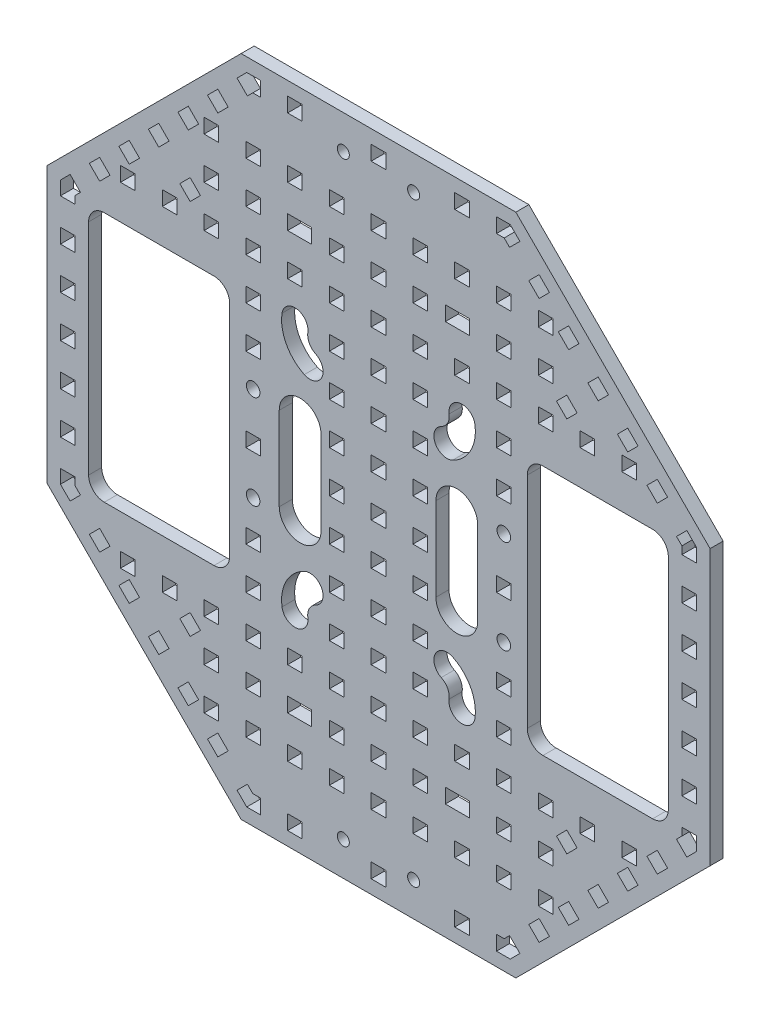
SolidWorks part; units mm, degrees
ref_plane "Plano frontal" through (0, 0, 0) normal (0, 0, 1) x (1, 0, 0)
ref_plane "Plano superior" through (0, 0, 0) normal (0, 1, 0) x (1, 0, 0)
ref_plane "Plano direito" through (0, 0, 0) normal (1, 0, 0) x (0, 0, -1)
sketch "Esboço1" plane through (0, 0, 0) normal (0, 0, 1) x (1, 0, 0)
  line L1 (63.5, -26.3026) -> (63.5, 26.3026)
  line L2 (63.5, 26.3026) -> (26.3026, 63.5)
  line L3 (26.3026, 63.5) -> (-26.3026, 63.5)
  line L4 (-26.3026, 63.5) -> (-63.5, 26.3026)
  line L5 (-63.5, 26.3026) -> (-63.5, -26.3026)
  line L6 (-63.5, -26.3026) -> (-26.3026, -63.5)
  line L7 (-26.3026, -63.5) -> (26.3026, -63.5)
  line L8 (26.3026, -63.5) -> (63.5, -26.3026)
  circle A0 centre (0, 0) radius 63.5 construction
  dimension "D1" = 127
extrude "Ressalto-extrusão1" add sketch "Esboço1" along normal blind 2.5
sketch "Esboço3"
sketch "Esboço2" plane through (0, 0, 0) normal (0, 0, -1) x (-1, 0, 0)
  line L0 (-42, 0) -> (42, 0) construction
  line L1 (-24, 0) -> (24, 0) construction
  line L2 (24, 0) -> (24, 9) construction
  line L3 (0, 0) -> (0, 75.734) construction
  line L4 (52.5, 24) -> (31.5, 24)
  line L5 (55.5, 21) -> (55.5, -21)
  line L6 (52.5, -24) -> (31.5, -24)
  line L7 (28.5, 21) -> (28.5, -21)
  line L8 (55.5, 24) -> (28.5, -24) construction
  line L9 (55.5, -24) -> (28.5, 24) construction
  line L10 (-55.5, -24) -> (-28.5, 24) construction
  line L11 (-55.5, 24) -> (-28.5, -24) construction
  line L12 (-24, 0) -> (-24, 9) construction
  line L13 (-28.5, 21) -> (-28.5, -21)
  line L14 (-52.5, -24) -> (-31.5, -24)
  line L15 (-55.5, 21) -> (-55.5, -21)
  line L16 (-52.5, 24) -> (-31.5, 24)
  line L17 (0, 0) -> (0, -57) construction
  line L18 (0, -57) -> (-6.731, -57) construction
  line L19 (0, 63.5) -> (0, 43.5) construction
  line L20 (-26.3026, 63.5) -> (26.3026, 63.5) construction
  line L29 (63.5, 0) -> (-63.5, 0) construction
  line L30 (63.5, 26.3026) -> (63.5, -26.3026) construction
  line L31 (-63.5, -26.3026) -> (-63.5, 26.3026) construction
  circle A0 centre (24, 9) radius 1.3
  circle A1 centre (24, -9) radius 1.3
  arc A2 (31.5, 24) -> (28.5, 21) centre (31.5, 21) ccw
  arc A3 (31.5, -24) -> (28.5, -21) centre (31.5, -21) cw
  arc A4 (55.5, -21) -> (52.5, -24) centre (52.5, -21) cw
  arc A5 (52.5, 24) -> (55.5, 21) centre (52.5, 21) cw
  arc A6 (-52.5, 24) -> (-55.5, 21) centre (-52.5, 21) ccw
  arc A7 (-55.5, -21) -> (-52.5, -24) centre (-52.5, -21) ccw
  arc A8 (-31.5, -24) -> (-28.5, -21) centre (-31.5, -21) ccw
  arc A9 (-31.5, 24) -> (-28.5, 21) centre (-31.5, 21) cw
  circle A10 centre (-24, -9) radius 1.3
  circle A11 centre (-24, 9) radius 1.3
  circle A12 centre (-6.731, -57) radius 1.15
  circle A13 centre (6.731, -57) radius 1.15
  circle A14 centre (6.731, 57) radius 1.15
  circle A15 centre (-6.731, 57) radius 1.15
  dimension "D6" = 3
  dimension "D8" = 6.731
  dimension "D12" = 9
  dimension "D1" = 42
  dimension "D2" = 48
  dimension "D3" = 27
  dimension "D4" = 24
  dimension "D5" = 9
  dimension "D7" = 57
extrude "Corte-extrusão1" cut sketch "Esboço2" against normal through all
sketch "Esboço4" plane through (0, 0, 2.5) normal (0, 0, 1) x (1, 0, 0)
  line L0 (0, 0) -> (36.0624, 36.0624) construction
  line L1 (0, 0) -> (36.0624, -36.0624) construction
  line L2 (0, 0) -> (-36.0624, -36.0624) construction
  line L3 (0, 0) -> (-36.0624, 36.0624) construction
  line L4 (-38.0423, 36.0624) -> (-34.0825, 36.0624) construction
  line L11 (-36.0624, 34.0825) -> (-36.0624, 38.0423) construction
  line L12 (-36.0624, 34.0825) -> (-34.0825, 36.0624)
  line L13 (-38.0423, 36.0624) -> (-36.0624, 34.0825)
  line L14 (-36.0624, 38.0423) -> (-34.0825, 36.0624)
  line L15 (-38.0423, 36.0624) -> (-36.0624, 38.0423)
  line L16 (34.0825, 36.0624) -> (38.0423, 36.0624) construction
  line L17 (36.0624, 34.0825) -> (36.0624, 38.0423) construction
  line L18 (36.0624, 34.0825) -> (38.0423, 36.0624)
  line L19 (34.0825, 36.0624) -> (36.0624, 34.0825)
  line L20 (36.0624, 38.0423) -> (38.0423, 36.0624)
  line L21 (34.0825, 36.0624) -> (36.0624, 38.0423)
  line L22 (34.0825, -36.0624) -> (38.0423, -36.0624) construction
  line L23 (36.0624, -38.0423) -> (36.0624, -34.0825) construction
  line L24 (36.0624, -38.0423) -> (38.0423, -36.0624)
  line L25 (34.0825, -36.0624) -> (36.0624, -38.0423)
  line L26 (36.0624, -34.0825) -> (38.0423, -36.0624)
  line L27 (34.0825, -36.0624) -> (36.0624, -34.0825)
  line L28 (-38.0423, -36.0624) -> (-34.0825, -36.0624) construction
  line L29 (-36.0624, -38.0423) -> (-36.0624, -34.0825) construction
  line L30 (-36.0624, -38.0423) -> (-34.0825, -36.0624)
  line L31 (-38.0423, -36.0624) -> (-36.0624, -38.0423)
  line L32 (-36.0624, -34.0825) -> (-34.0825, -36.0624)
  line L33 (-38.0423, -36.0624) -> (-36.0624, -34.0825)
  circle A0 centre (0, 0) radius 51 construction
  circle A1 centre (-36.0624, 36.0624) radius 1.65 construction
  circle A2 centre (36.0624, 36.0624) radius 1.65 construction
  circle A3 centre (36.0624, -36.0624) radius 1.65 construction
  circle A4 centre (-36.0624, -36.0624) radius 1.65 construction
  point P10 (0, 0)
  point P17 (0, 0)
  point P21 (-36.0624, 36.0624)
  point P26 (36.0624, 36.0624)
  point P31 (36.0624, -36.0624)
  point P36 (-36.0624, -36.0624)
  dimension "D1" = 4
  dimension "D2" = 4
  dimension "D4" = 2.8
  dimension "D5" = 2.8
  dimension "D6" = 2.8
  dimension "D7" = 2.8
extrude "Corte-extrusão2" cut sketch "Esboço4" against normal blind 10.5
sketch "Esboço5" plane through (0, 0, 0) normal (0, 0, -1) x (-1, 0, 0)
  line L0 (-44.9013, -44.9013) -> (-42.0729, -42.0729) construction
  line L1 (-26.3026, -63.5) -> (-63.5, -26.3026) construction
  line L2 (-47.7297, -34.4361) -> (-49.7096, -36.416)
  line L3 (-42.0729, -40.093) -> (-44.0528, -42.0729)
  line L4 (-42.0729, -40.093) -> (-40.093, -42.0729)
  line L5 (-40.093, -42.0729) -> (-42.0729, -44.0528)
  line L6 (-44.0528, -42.0729) -> (-42.0729, -44.0528)
  line L7 (-42.0729, -40.093) -> (-42.0729, -44.0528) construction
  line L8 (-40.093, -42.0729) -> (-44.0528, -42.0729) construction
  line L9 (-47.7297, -34.4361) -> (-45.7498, -36.416)
  line L10 (-45.7498, -36.416) -> (-47.7297, -38.3959)
  line L11 (-49.7096, -36.416) -> (-47.7297, -38.3959)
  line L12 (-47.7297, -34.4361) -> (-47.7297, -38.3959) construction
  line L13 (-45.7498, -36.416) -> (-49.7096, -36.416) construction
  line L14 (-53.3866, -28.7792) -> (-55.3665, -30.7591)
  line L15 (-53.3866, -28.7792) -> (-51.4067, -30.7591)
  line L16 (-51.4067, -30.7591) -> (-53.3866, -32.739)
  line L17 (-55.3665, -30.7591) -> (-53.3866, -32.739)
  line L18 (-53.3866, -28.7792) -> (-53.3866, -32.739) construction
  line L19 (-51.4067, -30.7591) -> (-55.3665, -30.7591) construction
  line L20 (-63.5, -26.3026) -> (-63.5, 26.3026) construction
  line L21 (63.5, 26.3026) -> (63.5, -26.3026) construction
  line L22 (-16, 24) -> (0, 24) construction
  line L23 (0, 24) -> (16, 24) construction
  line L24 (-9.4, 22.6) -> (-6.6, 25.4) construction
  line L25 (-9.4, 25.4) -> (-9.4, 22.6)
  line L26 (-9.4, 22.6) -> (-6.6, 22.6)
  line L27 (-9.4, 25.4) -> (-6.6, 22.6) construction
  line L28 (-30.7591, -51.4067) -> (-30.7591, -55.3665) construction
  line L29 (-28.7792, -53.3866) -> (-32.739, -53.3866) construction
  line L30 (-36.416, -45.7498) -> (-36.416, -49.7096) construction
  line L31 (-34.4361, -47.7297) -> (-38.3959, -47.7297) construction
  line L32 (-42.0729, -40.093) -> (-42.0729, -44.0528) construction
  line L33 (-40.093, -42.0729) -> (-44.0528, -42.0729) construction
  line L34 (-25.2256, -60.9) -> (-27.0822, -59.0434)
  line L35 (-25.1023, -57.0635) -> (-27.0822, -59.0434)
  line L36 (-9.4, 25.4) -> (-6.6, 25.4)
  line L37 (-6.6, 25.4) -> (-6.6, 22.6)
  line L38 (-30.7591, -55.3665) -> (-32.739, -53.3866)
  line L39 (-30.7591, -51.4067) -> (-32.739, -53.3866)
  line L40 (-28.7792, -53.3866) -> (-30.7591, -51.4067)
  line L41 (-28.7792, -53.3866) -> (-30.7591, -55.3665)
  line L42 (-36.416, -49.7096) -> (-38.3959, -47.7297)
  line L43 (-36.416, -45.7498) -> (-38.3959, -47.7297)
  line L44 (-34.4361, -47.7297) -> (-36.416, -45.7498)
  line L45 (-58.1, 6.6) -> (-60.9, 9.4) construction
  line L46 (-60.9, 6.6) -> (-58.1, 9.4) construction
  line L47 (-34.4361, -47.7297) -> (-36.416, -49.7096)
  line L48 (0, -63.5) -> (0, -59.5) construction
  line L49 (26.3026, -63.5) -> (-26.3026, -63.5) construction
  line L50 (-9.4, 6.6) -> (-6.6, 6.6)
  line L51 (1.4, -58.1) -> (-1.4, -58.1)
  line L52 (1.4, -58.1) -> (1.4, -60.9)
  line L53 (1.4, -60.9) -> (-1.4, -60.9)
  line L54 (-1.4, -58.1) -> (-1.4, -60.9)
  line L55 (1.4, -58.1) -> (-1.4, -60.9) construction
  line L56 (1.4, -60.9) -> (-1.4, -58.1) construction
  line L57 (-6.6, 9.4) -> (-6.6, 6.6)
  line L58 (-9.4, 9.4) -> (-6.6, 9.4)
  line L59 (-9.4, 9.4) -> (-9.4, 6.6)
  line L60 (-9.4, 6.6) -> (-6.6, 9.4) construction
  line L61 (-9.4, 9.4) -> (-6.6, 6.6) construction
  line L62 (-14.6, -58.1) -> (-17.4, -58.1)
  line L63 (-14.6, -58.1) -> (-14.6, -60.9)
  line L64 (-14.6, -60.9) -> (-17.4, -60.9)
  line L65 (-17.4, -58.1) -> (-17.4, -60.9)
  line L66 (-14.6, -58.1) -> (-17.4, -60.9) construction
  line L67 (-14.6, -60.9) -> (-17.4, -58.1) construction
  line L68 (-22.6, -58.1) -> (-24.0658, -58.1)
  line L69 (-22.6, -58.1) -> (-22.6, -60.9)
  line L70 (-22.6, -60.9) -> (-25.2256, -60.9)
  line L71 (6.6, 22.6) -> (9.4, 25.4) construction
  line L72 (6.6, 25.4) -> (6.6, 22.6)
  line L73 (6.6, 22.6) -> (9.4, 22.6)
  line L74 (6.6, 25.4) -> (9.4, 22.6) construction
  line L75 (6.6, 25.4) -> (9.4, 25.4)
  line L76 (9.4, 25.4) -> (9.4, 22.6)
  line L77 (-9.4, -1.4) -> (-6.6, -1.4)
  line L78 (-25.4, -58.1) -> (-25.4, -59.0434) [skipped]
  line L79 (-33.4, 46.6) -> (-30.6, 49.4) construction
  line L80 (-24.0658, -58.1) -> (-25.1023, -57.0635)
  line L81 (-33.4, 49.4) -> (-30.6, 46.6) construction
  line L82 (-23.5434, -59.0434) -> (-24, -59.5) construction
  line L83 (-25.4, 46.6) -> (-22.6, 49.4) construction
  line L84 (-24, -59.5) -> (-24.4566, -59.0434) construction
  line L85 (6.6, -25.4) -> (9.4, -22.6) construction
  line L86 (6.6, -22.6) -> (9.4, -25.4) construction
  line L87 (9.4, -25.4) -> (9.4, -22.6)
  line L88 (6.6, -25.4) -> (9.4, -25.4)
  line L89 (6.6, -22.6) -> (9.4, -22.6)
  line L90 (6.6, -25.4) -> (6.6, -22.6)
  line L91 (-9.4, -25.4) -> (-6.6, -22.6) construction
  line L92 (-9.4, -22.6) -> (-6.6, -25.4) construction
  line L93 (-6.6, -25.4) -> (-6.6, -22.6)
  line L94 (-9.4, -25.4) -> (-6.6, -25.4)
  line L95 (-9.4, -22.6) -> (-6.6, -22.6)
  line L96 (-9.4, -25.4) -> (-9.4, -22.6)
  line L97 (-60.25, 0) -> (60.25, 0) construction
  line L98 (0, 0) -> (0, 63.5) construction
  line L99 (-26.3026, 63.5) -> (26.3026, 63.5) construction
  line L100 (-25.4, 49.4) -> (-22.6, 46.6) construction
  line L101 (-6.6, 1.4) -> (-6.6, -1.4)
  line L102 (-9.4, 1.4) -> (-6.6, 1.4)
  line L103 (-9.4, 1.4) -> (-9.4, -1.4)
  line L104 (-9.4, -1.4) -> (-6.6, 1.4) construction
  line L105 (-9.4, 1.4) -> (-6.6, -1.4) construction
  line L106 (14.6, -60.9) -> (17.4, -58.1) construction
  line L107 (14.6, -58.1) -> (17.4, -60.9) construction
  line L108 (-9.4, -9.4) -> (-6.6, -9.4)
  line L109 (-6.6, -6.6) -> (-6.6, -9.4)
  line L110 (40.093, -42.0729) -> (44.0528, -42.0729) construction
  line L111 (42.0729, -40.093) -> (42.0729, -44.0528) construction
  line L112 (34.4361, -47.7297) -> (38.3959, -47.7297) construction
  line L113 (36.416, -45.7498) -> (36.416, -49.7096) construction
  line L114 (28.7792, -53.3866) -> (32.739, -53.3866) construction
  line L115 (30.7591, -51.4067) -> (30.7591, -55.3665) construction
  line L116 (-9.4, -6.6) -> (-6.6, -6.6)
  line L117 (-9.4, -6.6) -> (-9.4, -9.4)
  line L118 (-9.4, -9.4) -> (-6.6, -6.6) construction
  line L119 (51.4067, -30.7591) -> (55.3665, -30.7591) construction
  line L120 (53.3866, -28.7792) -> (53.3866, -32.739) construction
  line L121 (45.7498, -36.416) -> (49.7096, -36.416) construction
  line L122 (47.7297, -34.4361) -> (47.7297, -38.3959) construction
  line L123 (40.093, -42.0729) -> (44.0528, -42.0729) construction
  line L124 (42.0729, -40.093) -> (42.0729, -44.0528) construction
  line L125 (44.9013, -44.9013) -> (42.0729, -42.0729) construction
  line L126 (-9.4, -6.6) -> (-6.6, -9.4) construction
  line L127 (9.4, -6.6) -> (6.6, -9.4) construction
  line L128 (9.4, -9.4) -> (6.6, -6.6) construction
  line L129 (9.4, 1.4) -> (6.6, -1.4) construction
  line L130 (9.4, -1.4) -> (6.6, 1.4) construction
  line L131 (9.4, 9.4) -> (6.6, 6.6) construction
  line L132 (9.4, 6.6) -> (6.6, 9.4) construction
  line L133 (24.0658, -58.1) -> (25.1023, -57.0635)
  line L134 (60.9, -25.2256) -> (59.0434, -27.0822)
  line L135 (57.0635, -25.1023) -> (59.0434, -27.0822)
  line L136 (58.1, -6.6) -> (58.1, -9.4)
  line L137 (58.1, 1.4) -> (58.1, -1.4)
  line L138 (22.6, -60.9) -> (25.2256, -60.9)
  line L139 (22.6, -58.1) -> (22.6, -60.9)
  line L140 (22.6, -58.1) -> (24.0658, -58.1)
  line L141 (17.4, -58.1) -> (17.4, -60.9)
  line L142 (14.6, -60.9) -> (17.4, -60.9)
  line L143 (14.6, -58.1) -> (14.6, -60.9)
  line L144 (14.6, -58.1) -> (17.4, -58.1)
  line L145 (9.4, -6.6) -> (9.4, -9.4)
  line L146 (9.4, -6.6) -> (6.6, -6.6)
  line L147 (6.6, -6.6) -> (6.6, -9.4)
  line L148 (9.4, -9.4) -> (6.6, -9.4)
  line L149 (34.4361, -47.7297) -> (36.416, -49.7096)
  line L150 (40.093, -42.0729) -> (42.0729, -44.0528)
  line L151 (42.0729, -40.093) -> (44.0528, -42.0729)
  line L152 (34.4361, -47.7297) -> (36.416, -45.7498)
  line L153 (36.416, -45.7498) -> (38.3959, -47.7297)
  line L154 (36.416, -49.7096) -> (38.3959, -47.7297)
  line L155 (28.7792, -53.3866) -> (30.7591, -55.3665)
  line L156 (28.7792, -53.3866) -> (30.7591, -51.4067)
  line L157 (30.7591, -51.4067) -> (32.739, -53.3866)
  line L158 (30.7591, -55.3665) -> (32.739, -53.3866)
  line L159 (58.1, 1.4) -> (60.9, 1.4)
  line L160 (25.1023, -57.0635) -> (27.0822, -59.0434)
  line L161 (25.2256, -60.9) -> (27.0822, -59.0434)
  line L162 (60.9, 1.4) -> (60.9, -1.4)
  line L163 (58.1, -1.4) -> (60.9, -1.4)
  line L164 (58.1, -6.6) -> (60.9, -6.6)
  line L165 (60.9, -6.6) -> (60.9, -9.4)
  line L166 (55.3665, -30.7591) -> (53.3866, -32.739)
  line L167 (51.4067, -30.7591) -> (53.3866, -32.739)
  line L168 (53.3866, -28.7792) -> (51.4067, -30.7591)
  line L169 (53.3866, -28.7792) -> (55.3665, -30.7591)
  line L170 (49.7096, -36.416) -> (47.7297, -38.3959)
  line L171 (45.7498, -36.416) -> (47.7297, -38.3959)
  line L172 (47.7297, -34.4361) -> (45.7498, -36.416)
  line L173 (44.0528, -42.0729) -> (42.0729, -44.0528)
  line L174 (-58.1, 14.6) -> (-60.9, 17.4) construction
  line L175 (42.0729, -40.093) -> (40.093, -42.0729)
  line L176 (-60.9, 14.6) -> (-58.1, 17.4) construction
  line L177 (47.7297, -34.4361) -> (49.7096, -36.416)
  line L178 (44.9013, 44.9013) -> (42.0729, 42.0729) construction
  line L179 (42.0729, 40.093) -> (42.0729, 44.0528) construction
  line L180 (40.093, 42.0729) -> (44.0528, 42.0729) construction
  line L181 (47.7297, 34.4361) -> (47.7297, 38.3959) construction
  line L182 (45.7498, 36.416) -> (49.7096, 36.416) construction
  line L183 (53.3866, 28.7792) -> (53.3866, 32.739) construction
  line L184 (51.4067, 30.7591) -> (55.3665, 30.7591) construction
  line L185 (58.1, -9.4) -> (60.9, -9.4)
  line L186 (58.1, -14.6) -> (58.1, -17.4)
  line L187 (30.7591, 51.4067) -> (30.7591, 55.3665) construction
  line L188 (28.7792, 53.3866) -> (32.739, 53.3866) construction
  line L189 (36.416, 45.7498) -> (36.416, 49.7096) construction
  line L190 (34.4361, 47.7297) -> (38.3959, 47.7297) construction
  line L191 (42.0729, 40.093) -> (42.0729, 44.0528) construction
  line L192 (40.093, 42.0729) -> (44.0528, 42.0729) construction
  line L193 (9.4, 1.4) -> (9.4, -1.4)
  line L194 (9.4, 1.4) -> (6.6, 1.4)
  line L195 (14.6, 58.1) -> (17.4, 60.9) construction
  line L196 (14.6, 60.9) -> (17.4, 58.1) construction
  line L197 (58.1, -14.6) -> (60.9, -14.6)
  line L198 (60.9, -14.6) -> (60.9, -17.4)
  line L199 (58.1, -17.4) -> (60.9, -17.4)
  line L200 (58.1, -22.6) -> (58.1, -24.0658)
  line L201 (58.1, -22.6) -> (60.9, -22.6)
  line L202 (60.9, -22.6) -> (60.9, -25.2256)
  line L203 (58.1, -24.0658) -> (57.0635, -25.1023)
  line L204 (58.1, 24.0658) -> (57.0635, 25.1023)
  line L205 (-14.6, 60.9) -> (-17.4, 58.1) construction
  line L206 (-14.6, 58.1) -> (-17.4, 60.9) construction
  line L207 (6.6, 1.4) -> (6.6, -1.4)
  line L208 (9.4, -1.4) -> (6.6, -1.4)
  line L209 (1.4, 60.9) -> (-1.4, 58.1) construction
  line L210 (1.4, 58.1) -> (-1.4, 60.9) construction
  line L211 (0, 63.5) -> (0, 59.5) construction
  line L212 (-40.093, 42.0729) -> (-44.0528, 42.0729) construction
  line L213 (-42.0729, 40.093) -> (-42.0729, 44.0528) construction
  line L214 (-34.4361, 47.7297) -> (-38.3959, 47.7297) construction
  line L215 (-36.416, 45.7498) -> (-36.416, 49.7096) construction
  line L216 (-28.7792, 53.3866) -> (-32.739, 53.3866) construction
  line L217 (-30.7591, 51.4067) -> (-30.7591, 55.3665) construction
  line L218 (60.9, 22.6) -> (60.9, 25.2256)
  line L219 (58.1, 22.6) -> (60.9, 22.6)
  line L220 (-51.4067, 30.7591) -> (-55.3665, 30.7591) construction
  line L221 (-53.3866, 28.7792) -> (-53.3866, 32.739) construction
  line L222 (-45.7498, 36.416) -> (-49.7096, 36.416) construction
  line L223 (-47.7297, 34.4361) -> (-47.7297, 38.3959) construction
  line L224 (-40.093, 42.0729) -> (-44.0528, 42.0729) construction
  line L225 (-42.0729, 40.093) -> (-42.0729, 44.0528) construction
  line L226 (-44.9013, 44.9013) -> (-42.0729, 42.0729) construction
  line L227 (47.7297, 34.4361) -> (49.7096, 36.416)
  line L228 (42.0729, 40.093) -> (44.0528, 42.0729)
  line L229 (42.0729, 40.093) -> (40.093, 42.0729)
  line L230 (40.093, 42.0729) -> (42.0729, 44.0528)
  line L231 (44.0528, 42.0729) -> (42.0729, 44.0528)
  line L232 (47.7297, 34.4361) -> (45.7498, 36.416)
  line L233 (45.7498, 36.416) -> (47.7297, 38.3959)
  line L234 (49.7096, 36.416) -> (47.7297, 38.3959)
  line L235 (53.3866, 28.7792) -> (55.3665, 30.7591)
  line L236 (53.3866, 28.7792) -> (51.4067, 30.7591)
  line L237 (51.4067, 30.7591) -> (53.3866, 32.739)
  line L238 (55.3665, 30.7591) -> (53.3866, 32.739)
  line L239 (58.1, 22.6) -> (58.1, 24.0658)
  line L240 (58.1, 17.4) -> (60.9, 17.4)
  line L241 (60.9, 14.6) -> (60.9, 17.4)
  line L242 (58.1, 14.6) -> (60.9, 14.6)
  line L243 (25.2256, 60.9) -> (27.0822, 59.0434)
  line L244 (25.1023, 57.0635) -> (27.0822, 59.0434)
  line L245 (58.1, 14.6) -> (58.1, 17.4)
  line L246 (30.7591, 55.3665) -> (32.739, 53.3866)
  line L247 (30.7591, 51.4067) -> (32.739, 53.3866)
  line L248 (28.7792, 53.3866) -> (30.7591, 51.4067)
  line L249 (28.7792, 53.3866) -> (30.7591, 55.3665)
  line L250 (36.416, 49.7096) -> (38.3959, 47.7297)
  line L251 (36.416, 45.7498) -> (38.3959, 47.7297)
  line L252 (34.4361, 47.7297) -> (36.416, 45.7498)
  line L253 (-60.9, -14.6) -> (-58.1, -17.4) construction
  line L254 (-58.1, -14.6) -> (-60.9, -17.4) construction
  line L255 (34.4361, 47.7297) -> (36.416, 49.7096)
  line L256 (9.4, 9.4) -> (9.4, 6.6)
  line L257 (9.4, 9.4) -> (6.6, 9.4)
  line L258 (6.6, 9.4) -> (6.6, 6.6)
  line L259 (9.4, 6.6) -> (6.6, 6.6)
  line L260 (14.6, 58.1) -> (17.4, 58.1)
  line L261 (14.6, 58.1) -> (14.6, 60.9)
  line L262 (14.6, 60.9) -> (17.4, 60.9)
  line L263 (17.4, 58.1) -> (17.4, 60.9)
  line L264 (22.6, 58.1) -> (24.0658, 58.1)
  line L265 (22.6, 58.1) -> (22.6, 60.9)
  line L266 (22.6, 60.9) -> (25.2256, 60.9)
  line L267 (24.0658, 58.1) -> (25.1023, 57.0635)
  line L268 (58.1, 9.4) -> (60.9, 9.4)
  line L269 (60.9, 6.6) -> (60.9, 9.4)
  line L270 (58.1, 6.6) -> (60.9, 6.6)
  line L271 (58.1, 6.6) -> (58.1, 9.4)
  line L272 (57.0635, 25.1023) -> (59.0434, 27.0822)
  line L273 (60.9, 25.2256) -> (59.0434, 27.0822)
  line L274 (63.5, 0) -> (59.5, 0) construction
  line L275 (58.1, 1.4) -> (60.9, -1.4) construction
  line L276 (60.9, 1.4) -> (58.1, -1.4) construction
  line L277 (58.1, -6.6) -> (60.9, -9.4) construction
  line L278 (60.9, -6.6) -> (58.1, -9.4) construction
  line L279 (58.1, -14.6) -> (60.9, -17.4) construction
  line L280 (60.9, -14.6) -> (58.1, -17.4) construction
  line L281 (60.9, 14.6) -> (58.1, 17.4) construction
  line L282 (-24.0658, 58.1) -> (-25.1023, 57.0635)
  line L283 (-22.6, 60.9) -> (-25.2256, 60.9)
  line L284 (-22.6, 58.1) -> (-22.6, 60.9)
  line L285 (-22.6, 58.1) -> (-24.0658, 58.1)
  line L286 (-17.4, 58.1) -> (-17.4, 60.9)
  line L287 (-14.6, 60.9) -> (-17.4, 60.9)
  line L288 (-14.6, 58.1) -> (-14.6, 60.9)
  line L289 (-14.6, 58.1) -> (-17.4, 58.1)
  line L293 (-1.4, 58.1) -> (-1.4, 60.9)
  line L294 (1.4, 60.9) -> (-1.4, 60.9)
  line L295 (1.4, 58.1) -> (1.4, 60.9)
  line L296 (1.4, 58.1) -> (-1.4, 58.1)
  line L298 (-34.4361, 47.7297) -> (-36.416, 49.7096)
  line L299 (-40.093, 42.0729) -> (-42.0729, 44.0528)
  line L300 (-42.0729, 40.093) -> (-44.0528, 42.0729)
  line L301 (-34.4361, 47.7297) -> (-36.416, 45.7498)
  line L302 (-36.416, 45.7498) -> (-38.3959, 47.7297)
  line L303 (-36.416, 49.7096) -> (-38.3959, 47.7297)
  line L304 (-28.7792, 53.3866) -> (-30.7591, 55.3665)
  line L305 (-28.7792, 53.3866) -> (-30.7591, 51.4067)
  line L306 (-30.7591, 51.4067) -> (-32.739, 53.3866)
  line L307 (-30.7591, 55.3665) -> (-32.739, 53.3866)
  line L308 (58.1, 14.6) -> (60.9, 17.4) construction
  line L309 (-25.1023, 57.0635) -> (-27.0822, 59.0434)
  line L310 (-25.2256, 60.9) -> (-27.0822, 59.0434)
  line L311 (60.9, 6.6) -> (58.1, 9.4) construction
  line L312 (58.1, 6.6) -> (60.9, 9.4) construction
  line L315 (-55.3665, 30.7591) -> (-53.3866, 32.739)
  line L316 (-51.4067, 30.7591) -> (-53.3866, 32.739)
  line L317 (-53.3866, 28.7792) -> (-51.4067, 30.7591)
  line L318 (-53.3866, 28.7792) -> (-55.3665, 30.7591)
  line L319 (-49.7096, 36.416) -> (-47.7297, 38.3959)
  line L320 (-45.7498, 36.416) -> (-47.7297, 38.3959)
  line L321 (-47.7297, 34.4361) -> (-45.7498, 36.416)
  line L322 (-44.0528, 42.0729) -> (-42.0729, 44.0528)
  line L323 (-60.9, -6.6) -> (-58.1, -9.4) construction
  line L324 (-42.0729, 40.093) -> (-40.093, 42.0729)
  line L325 (-58.1, -6.6) -> (-60.9, -9.4) construction
  line L326 (-47.7297, 34.4361) -> (-49.7096, 36.416)
  line L327 (-17.4, 46.6) -> (-14.6, 49.4) construction
  line L328 (1.4, 1.4) -> (-1.4, 1.4)
  line L329 (1.4, 1.4) -> (1.4, -1.4)
  line L330 (1.4, -1.4) -> (-1.4, -1.4)
  line L331 (-1.4, 1.4) -> (-1.4, -1.4)
  line L332 (1.4, 1.4) -> (-1.4, -1.4) construction
  line L333 (1.4, -1.4) -> (-1.4, 1.4) construction
  line L345 (25.4, 1.4) -> (22.6, -1.4) construction
  line L346 (25.4, -1.4) -> (22.6, 1.4) construction
  line L347 (25.4, 1.4) -> (25.4, -1.4)
  line L348 (25.4, 1.4) -> (22.6, 1.4)
  line L349 (22.6, 1.4) -> (22.6, -1.4)
  line L350 (25.4, -1.4) -> (22.6, -1.4)
  line L351 (33.4, 1.4) -> (30.6, -1.4) construction
  line L352 (33.4, -1.4) -> (30.6, 1.4) construction
  line L353 (33.4, 1.4) -> (33.4, -1.4) [skipped]
  line L354 (33.4, 1.4) -> (30.6, 1.4) [skipped]
  line L355 (30.6, 1.4) -> (30.6, -1.4) [skipped]
  line L356 (33.4, -1.4) -> (30.6, -1.4) [skipped]
  line L357 (41.4, 1.4) -> (38.6, -1.4) construction
  line L358 (41.4, -1.4) -> (38.6, 1.4) construction
  line L359 (41.4, 1.4) -> (41.4, -1.4) [skipped]
  line L360 (41.4, 1.4) -> (38.6, 1.4) [skipped]
  line L361 (38.6, 1.4) -> (38.6, -1.4) [skipped]
  line L362 (41.4, -1.4) -> (38.6, -1.4) [skipped]
  line L363 (49.4, 1.4) -> (46.6, -1.4) construction
  line L364 (49.4, -1.4) -> (46.6, 1.4) construction
  line L365 (49.4, 1.4) -> (49.4, -1.4) [skipped]
  line L366 (49.4, 1.4) -> (46.6, 1.4) [skipped]
  line L367 (46.6, 1.4) -> (46.6, -1.4) [skipped]
  line L368 (49.4, -1.4) -> (46.6, -1.4) [skipped]
  line L387 (33.4, 9.4) -> (30.6, 6.6) construction
  line L388 (33.4, 6.6) -> (30.6, 9.4) construction
  line L389 (33.4, 9.4) -> (33.4, 6.6) [skipped]
  line L390 (33.4, 9.4) -> (30.6, 9.4) [skipped]
  line L391 (30.6, 9.4) -> (30.6, 6.6) [skipped]
  line L392 (33.4, 6.6) -> (30.6, 6.6) [skipped]
  line L393 (41.4, 9.4) -> (38.6, 6.6) construction
  line L394 (41.4, 6.6) -> (38.6, 9.4) construction
  line L395 (41.4, 9.4) -> (41.4, 6.6) [skipped]
  line L396 (41.4, 9.4) -> (38.6, 9.4) [skipped]
  line L397 (38.6, 9.4) -> (38.6, 6.6) [skipped]
  line L398 (41.4, 6.6) -> (38.6, 6.6) [skipped]
  line L399 (49.4, 9.4) -> (46.6, 6.6) construction
  line L400 (49.4, 6.6) -> (46.6, 9.4) construction
  line L401 (49.4, 9.4) -> (49.4, 6.6) [skipped]
  line L402 (49.4, 9.4) -> (46.6, 9.4) [skipped]
  line L403 (46.6, 9.4) -> (46.6, 6.6) [skipped]
  line L404 (49.4, 6.6) -> (46.6, 6.6) [skipped]
  line L405 (9.4, 17.4) -> (6.6, 14.6) construction
  line L406 (9.4, 14.6) -> (6.6, 17.4) construction
  line L407 (9.4, 17.4) -> (9.4, 14.6)
  line L408 (9.4, 17.4) -> (6.6, 17.4)
  line L409 (6.6, 17.4) -> (6.6, 14.6)
  line L410 (9.4, 14.6) -> (6.6, 14.6)
  line L411 (17.4, 17.4) -> (14.6, 14.6) construction
  line L412 (17.4, 14.6) -> (14.6, 17.4) construction
  line L413 (17.4, 17.4) -> (17.4, 14.6) construction
  line L414 (17.4, 17.4) -> (14.6, 17.4) construction
  line L415 (14.6, 17.4) -> (14.6, 14.6) construction
  line L416 (17.4, 14.6) -> (14.6, 14.6) construction
  line L417 (25.4, 17.4) -> (22.6, 14.6) construction
  line L418 (25.4, 14.6) -> (22.6, 17.4) construction
  line L419 (25.4, 17.4) -> (25.4, 14.6)
  line L420 (25.4, 17.4) -> (22.6, 17.4)
  line L421 (22.6, 17.4) -> (22.6, 14.6)
  line L422 (25.4, 14.6) -> (22.6, 14.6)
  line L423 (33.4, 17.4) -> (30.6, 14.6) construction
  line L424 (33.4, 14.6) -> (30.6, 17.4) construction
  line L425 (33.4, 17.4) -> (33.4, 14.6) [skipped]
  line L426 (33.4, 17.4) -> (30.6, 17.4) [skipped]
  line L427 (30.6, 17.4) -> (30.6, 14.6) [skipped]
  line L428 (33.4, 14.6) -> (30.6, 14.6) [skipped]
  line L429 (41.4, 17.4) -> (38.6, 14.6) construction
  line L430 (41.4, 14.6) -> (38.6, 17.4) construction
  line L431 (41.4, 17.4) -> (41.4, 14.6) [skipped]
  line L432 (41.4, 17.4) -> (38.6, 17.4) [skipped]
  line L433 (38.6, 17.4) -> (38.6, 14.6) [skipped]
  line L434 (41.4, 14.6) -> (38.6, 14.6) [skipped]
  line L435 (49.4, 17.4) -> (46.6, 14.6) construction
  line L436 (49.4, 14.6) -> (46.6, 17.4) construction
  line L437 (49.4, 17.4) -> (49.4, 14.6) [skipped]
  line L438 (49.4, 17.4) -> (46.6, 17.4) [skipped]
  line L439 (46.6, 17.4) -> (46.6, 14.6) [skipped]
  line L440 (49.4, 14.6) -> (46.6, 14.6) [skipped]
  line L441 (9.4, 25.4) -> (6.6, 22.6) construction
  line L442 (9.4, 22.6) -> (6.6, 25.4) construction
  line L443 (9.4, 25.4) -> (9.4, 22.6) [skipped]
  line L444 (9.4, 25.4) -> (6.6, 25.4) [skipped]
  line L445 (6.6, 25.4) -> (6.6, 22.6) [skipped]
  line L446 (9.4, 22.6) -> (6.6, 22.6) [skipped]
  line L447 (17.4, 25.4) -> (14.6, 22.6) construction
  line L448 (17.4, 22.6) -> (14.6, 25.4) construction
  line L449 (17.4, 25.4) -> (17.4, 22.6)
  line L450 (17.4, 25.4) -> (14.6, 25.4)
  line L451 (14.6, 25.4) -> (14.6, 22.6)
  line L452 (17.4, 22.6) -> (14.6, 22.6)
  line L453 (25.4, 25.4) -> (22.6, 22.6) construction
  line L454 (25.4, 22.6) -> (22.6, 25.4) construction
  line L455 (25.4, 25.4) -> (25.4, 22.6)
  line L456 (25.4, 25.4) -> (22.6, 25.4)
  line L457 (22.6, 25.4) -> (22.6, 22.6)
  line L458 (25.4, 22.6) -> (22.6, 22.6)
  line L459 (33.4, 25.4) -> (30.6, 22.6) construction
  line L460 (33.4, 22.6) -> (30.6, 25.4) construction
  line L461 (33.4, 25.4) -> (33.4, 22.6) [skipped]
  line L462 (33.4, 25.4) -> (30.6, 25.4) [skipped]
  line L463 (30.6, 25.4) -> (30.6, 22.6) [skipped]
  line L464 (33.4, 22.6) -> (30.6, 22.6) [skipped]
  line L465 (41.4, 25.4) -> (38.6, 22.6) construction
  line L466 (41.4, 22.6) -> (38.6, 25.4) construction
  line L467 (41.4, 25.4) -> (41.4, 22.6) [skipped]
  line L468 (41.4, 25.4) -> (38.6, 25.4) [skipped]
  line L469 (38.6, 25.4) -> (38.6, 22.6) [skipped]
  line L470 (41.4, 22.6) -> (38.6, 22.6) [skipped]
  line L471 (49.4, 25.4) -> (46.6, 22.6) construction
  line L472 (49.4, 22.6) -> (46.6, 25.4) construction
  line L473 (49.4, 25.4) -> (49.4, 22.6) [skipped]
  line L474 (49.4, 25.4) -> (46.6, 25.4) [skipped]
  line L475 (46.6, 25.4) -> (46.6, 22.6) [skipped]
  line L476 (49.4, 22.6) -> (46.6, 22.6) [skipped]
  line L477 (9.4, 33.4) -> (6.6, 30.6) construction
  line L478 (9.4, 30.6) -> (6.6, 33.4) construction
  line L479 (9.4, 33.4) -> (9.4, 30.6)
  line L480 (9.4, 33.4) -> (6.6, 33.4)
  line L481 (6.6, 33.4) -> (6.6, 30.6)
  line L482 (9.4, 30.6) -> (6.6, 30.6)
  line L483 (17.4, 33.4) -> (14.6, 30.6) construction
  line L484 (17.4, 30.6) -> (14.6, 33.4) construction
  line L485 (17.4, 33.4) -> (17.4, 30.6)
  line L486 (17.4, 33.4) -> (14.6, 33.4)
  line L487 (14.6, 33.4) -> (14.6, 30.6)
  line L488 (17.4, 30.6) -> (14.6, 30.6)
  line L489 (25.4, 33.4) -> (22.6, 30.6) construction
  line L490 (25.4, 30.6) -> (22.6, 33.4) construction
  line L491 (25.4, 33.4) -> (25.4, 30.6)
  line L492 (25.4, 33.4) -> (22.6, 33.4)
  line L493 (22.6, 33.4) -> (22.6, 30.6)
  line L494 (25.4, 30.6) -> (22.6, 30.6)
  line L495 (33.4, 33.4) -> (30.6, 30.6) construction
  line L496 (33.4, 30.6) -> (30.6, 33.4) construction
  line L497 (33.4, 33.4) -> (33.4, 30.6)
  line L498 (33.4, 33.4) -> (30.6, 33.4)
  line L499 (30.6, 33.4) -> (30.6, 30.6)
  line L500 (33.4, 30.6) -> (30.6, 30.6)
  line L501 (41.4, 33.4) -> (38.6, 30.6) construction
  line L502 (41.4, 30.6) -> (38.6, 33.4) construction
  line L503 (41.4, 33.4) -> (41.4, 30.6)
  line L504 (41.4, 33.4) -> (38.6, 33.4)
  line L505 (38.6, 33.4) -> (38.6, 30.6)
  line L506 (41.4, 30.6) -> (38.6, 30.6)
  line L507 (49.4, 33.4) -> (46.6, 30.6) construction
  line L508 (49.4, 30.6) -> (46.6, 33.4) construction
  line L509 (49.4, 33.4) -> (49.4, 30.6)
  line L510 (49.4, 33.4) -> (46.6, 33.4)
  line L511 (46.6, 33.4) -> (46.6, 30.6)
  line L512 (49.4, 30.6) -> (46.6, 30.6)
  line L513 (9.4, 41.4) -> (6.6, 38.6) construction
  line L514 (9.4, 38.6) -> (6.6, 41.4) construction
  line L515 (9.4, 41.4) -> (9.4, 38.6)
  line L516 (9.4, 41.4) -> (6.6, 41.4)
  line L517 (6.6, 41.4) -> (6.6, 38.6)
  line L518 (9.4, 38.6) -> (6.6, 38.6)
  line L519 (17.4, 41.4) -> (14.6, 38.6) construction
  line L520 (17.4, 38.6) -> (14.6, 41.4) construction
  line L521 (17.4, 41.4) -> (17.4, 38.6)
  line L522 (17.4, 41.4) -> (14.6, 41.4)
  line L523 (14.6, 41.4) -> (14.6, 38.6)
  line L524 (17.4, 38.6) -> (14.6, 38.6)
  line L525 (25.4, 41.4) -> (22.6, 38.6) construction
  line L526 (25.4, 38.6) -> (22.6, 41.4) construction
  line L527 (25.4, 41.4) -> (25.4, 38.6)
  line L528 (25.4, 41.4) -> (22.6, 41.4)
  line L529 (22.6, 41.4) -> (22.6, 38.6)
  line L530 (25.4, 38.6) -> (22.6, 38.6)
  line L531 (33.4, 41.4) -> (30.6, 38.6) construction
  line L532 (33.4, 38.6) -> (30.6, 41.4) construction
  line L533 (33.4, 41.4) -> (33.4, 38.6)
  line L534 (33.4, 41.4) -> (30.6, 41.4)
  line L535 (30.6, 41.4) -> (30.6, 38.6)
  line L536 (33.4, 38.6) -> (30.6, 38.6)
  line L537 (41.4, 41.4) -> (38.6, 38.6) construction
  line L538 (41.4, 38.6) -> (38.6, 41.4) construction
  line L539 (41.4, 41.4) -> (41.4, 38.6) [skipped]
  line L540 (41.4, 41.4) -> (38.6, 41.4) [skipped]
  line L541 (38.6, 41.4) -> (38.6, 38.6) [skipped]
  line L542 (41.4, 38.6) -> (38.6, 38.6) [skipped]
  line L543 (49.4, 41.4) -> (46.6, 38.6) construction
  line L544 (49.4, 38.6) -> (46.6, 41.4) construction
  line L545 (49.4, 41.4) -> (49.4, 38.6) [skipped]
  line L546 (49.4, 41.4) -> (46.6, 41.4) [skipped]
  line L547 (46.6, 41.4) -> (46.6, 38.6) [skipped]
  line L548 (49.4, 38.6) -> (46.6, 38.6) [skipped]
  line L549 (9.4, 49.4) -> (6.6, 46.6) construction
  line L550 (9.4, 46.6) -> (6.6, 49.4) construction
  line L551 (9.4, 49.4) -> (9.4, 46.6)
  line L552 (9.4, 49.4) -> (6.6, 49.4)
  line L553 (6.6, 49.4) -> (6.6, 46.6)
  line L554 (9.4, 46.6) -> (6.6, 46.6)
  line L555 (17.4, 49.4) -> (14.6, 46.6) construction
  line L556 (17.4, 46.6) -> (14.6, 49.4) construction
  line L557 (17.4, 49.4) -> (17.4, 46.6)
  line L558 (17.4, 49.4) -> (14.6, 49.4)
  line L559 (14.6, 49.4) -> (14.6, 46.6)
  line L560 (17.4, 46.6) -> (14.6, 46.6)
  line L561 (25.4, 49.4) -> (22.6, 46.6) construction
  line L562 (25.4, 46.6) -> (22.6, 49.4) construction
  line L563 (25.4, 49.4) -> (25.4, 46.6)
  line L564 (25.4, 49.4) -> (22.6, 49.4)
  line L565 (22.6, 49.4) -> (22.6, 46.6)
  line L566 (25.4, 46.6) -> (22.6, 46.6)
  line L567 (33.4, 49.4) -> (30.6, 46.6) construction
  line L568 (33.4, 46.6) -> (30.6, 49.4) construction
  line L569 (33.4, 49.4) -> (33.4, 46.6)
  line L570 (33.4, 49.4) -> (30.6, 49.4)
  line L571 (30.6, 49.4) -> (30.6, 46.6)
  line L572 (33.4, 46.6) -> (30.6, 46.6)
  line L573 (41.4, 49.4) -> (38.6, 46.6) construction
  line L574 (41.4, 46.6) -> (38.6, 49.4) construction
  line L575 (41.4, 49.4) -> (41.4, 46.6) [skipped]
  line L576 (41.4, 49.4) -> (38.6, 49.4) [skipped]
  line L577 (38.6, 49.4) -> (38.6, 46.6) [skipped]
  line L578 (41.4, 46.6) -> (38.6, 46.6) [skipped]
  line L579 (49.4, 49.4) -> (46.6, 46.6) construction
  line L580 (49.4, 46.6) -> (46.6, 49.4) construction
  line L581 (49.4, 49.4) -> (49.4, 46.6) [skipped]
  line L582 (49.4, 49.4) -> (46.6, 49.4) [skipped]
  line L583 (46.6, 49.4) -> (46.6, 46.6) [skipped]
  line L584 (49.4, 46.6) -> (46.6, 46.6) [skipped]
  line L585 (1.4, 9.4) -> (-1.4, 6.6) construction
  line L586 (1.4, 6.6) -> (-1.4, 9.4) construction
  line L587 (1.4, 9.4) -> (1.4, 6.6)
  line L588 (1.4, 9.4) -> (-1.4, 9.4)
  line L589 (-1.4, 9.4) -> (-1.4, 6.6)
  line L590 (1.4, 6.6) -> (-1.4, 6.6)
  line L591 (1.4, 17.4) -> (-1.4, 14.6) construction
  line L592 (1.4, 14.6) -> (-1.4, 17.4) construction
  line L593 (1.4, 17.4) -> (1.4, 14.6)
  line L594 (1.4, 17.4) -> (-1.4, 17.4)
  line L595 (-1.4, 17.4) -> (-1.4, 14.6)
  line L596 (1.4, 14.6) -> (-1.4, 14.6)
  line L597 (1.4, 25.4) -> (-1.4, 22.6) construction
  line L598 (1.4, 22.6) -> (-1.4, 25.4) construction
  line L599 (1.4, 25.4) -> (1.4, 22.6)
  line L600 (1.4, 25.4) -> (-1.4, 25.4)
  line L601 (-1.4, 25.4) -> (-1.4, 22.6)
  line L602 (1.4, 22.6) -> (-1.4, 22.6)
  line L603 (1.4, 33.4) -> (-1.4, 30.6) construction
  line L604 (1.4, 30.6) -> (-1.4, 33.4) construction
  line L605 (1.4, 33.4) -> (1.4, 30.6)
  line L606 (1.4, 33.4) -> (-1.4, 33.4)
  line L607 (-1.4, 33.4) -> (-1.4, 30.6)
  line L608 (1.4, 30.6) -> (-1.4, 30.6)
  line L609 (1.4, 41.4) -> (-1.4, 38.6) construction
  line L610 (1.4, 38.6) -> (-1.4, 41.4) construction
  line L611 (1.4, 41.4) -> (1.4, 38.6)
  line L612 (1.4, 41.4) -> (-1.4, 41.4)
  line L613 (-1.4, 41.4) -> (-1.4, 38.6)
  line L614 (1.4, 38.6) -> (-1.4, 38.6)
  line L615 (1.4, 49.4) -> (-1.4, 46.6) construction
  line L616 (1.4, 46.6) -> (-1.4, 49.4) construction
  line L617 (1.4, 49.4) -> (1.4, 46.6)
  line L618 (1.4, 49.4) -> (-1.4, 49.4)
  line L619 (-1.4, 49.4) -> (-1.4, 46.6)
  line L620 (1.4, 46.6) -> (-1.4, 46.6)
  line L621 (-17.4, 49.4) -> (-14.6, 46.6) construction
  line L622 (-9.4, 46.6) -> (-6.6, 49.4) construction
  line L623 (-9.4, 49.4) -> (-6.6, 46.6) construction
  line L624 (-33.4, 38.6) -> (-30.6, 41.4) construction
  line L625 (-33.4, 41.4) -> (-30.6, 38.6) construction
  line L626 (-25.4, 38.6) -> (-22.6, 41.4) construction
  line L627 (-25.4, 41.4) -> (-22.6, 38.6) construction
  line L628 (-17.4, 38.6) -> (-14.6, 41.4) construction
  line L629 (-17.4, 41.4) -> (-14.6, 38.6) construction
  line L630 (-9.4, 38.6) -> (-6.6, 41.4) construction
  line L631 (-9.4, 41.4) -> (-6.6, 38.6) construction
  line L632 (-33.4, 46.6) -> (-30.6, 46.6)
  line L633 (-30.6, 49.4) -> (-30.6, 46.6)
  line L634 (-33.4, 49.4) -> (-30.6, 49.4)
  line L635 (-33.4, 49.4) -> (-33.4, 46.6)
  line L636 (-25.4, 46.6) -> (-22.6, 46.6)
  line L637 (-22.6, 49.4) -> (-22.6, 46.6)
  line L638 (-25.4, 49.4) -> (-22.6, 49.4)
  line L639 (-25.4, 49.4) -> (-25.4, 46.6)
  line L640 (-17.4, 46.6) -> (-14.6, 46.6)
  line L641 (-14.6, 49.4) -> (-14.6, 46.6)
  line L642 (-17.4, 49.4) -> (-14.6, 49.4)
  line L643 (-17.4, 49.4) -> (-17.4, 46.6)
  line L644 (-9.4, 46.6) -> (-6.6, 46.6)
  line L645 (-6.6, 49.4) -> (-6.6, 46.6)
  line L646 (-9.4, 49.4) -> (-6.6, 49.4)
  line L647 (-9.4, 49.4) -> (-9.4, 46.6)
  line L648 (-33.4, 38.6) -> (-30.6, 38.6)
  line L649 (-30.6, 41.4) -> (-30.6, 38.6)
  line L650 (-33.4, 41.4) -> (-30.6, 41.4)
  line L651 (-33.4, 41.4) -> (-33.4, 38.6)
  line L652 (-25.4, 38.6) -> (-22.6, 38.6)
  line L653 (-22.6, 41.4) -> (-22.6, 38.6)
  line L654 (-25.4, 41.4) -> (-22.6, 41.4)
  line L655 (-25.4, 41.4) -> (-25.4, 38.6)
  line L656 (-17.4, 38.6) -> (-14.6, 38.6)
  line L657 (-14.6, 41.4) -> (-14.6, 38.6)
  line L658 (-17.4, 41.4) -> (-14.6, 41.4)
  line L659 (-17.4, 41.4) -> (-17.4, 38.6)
  line L660 (-9.4, 38.6) -> (-6.6, 38.6)
  line L661 (-6.6, 41.4) -> (-6.6, 38.6)
  line L662 (-9.4, 41.4) -> (-6.6, 41.4)
  line L663 (-9.4, 41.4) -> (-9.4, 38.6)
  line L664 (-49.4, 30.6) -> (-46.6, 33.4) construction
  line L665 (-49.4, 33.4) -> (-46.6, 30.6) construction
  line L666 (-41.4, 30.6) -> (-38.6, 33.4) construction
  line L667 (-41.4, 33.4) -> (-38.6, 30.6) construction
  line L668 (-33.4, 30.6) -> (-30.6, 33.4) construction
  line L669 (-33.4, 33.4) -> (-30.6, 30.6) construction
  line L670 (-25.4, 30.6) -> (-22.6, 33.4) construction
  line L671 (-25.4, 33.4) -> (-22.6, 30.6) construction
  line L672 (-17.4, 30.6) -> (-14.6, 33.4) construction
  line L673 (-17.4, 33.4) -> (-14.6, 30.6) construction
  line L674 (-9.4, 30.6) -> (-6.6, 33.4) construction
  line L675 (-9.4, 33.4) -> (-6.6, 30.6) construction
  line L676 (-25.4, 22.6) -> (-22.6, 25.4) construction
  line L677 (-25.4, 25.4) -> (-22.6, 22.6) construction
  line L678 (-17.4, 22.6) -> (-14.6, 25.4) construction
  line L679 (-17.4, 25.4) -> (-14.6, 22.6) construction
  line L680 (-25.4, 14.6) -> (-22.6, 17.4) construction
  line L681 (-25.4, 17.4) -> (-22.6, 14.6) construction
  line L682 (-17.4, 14.6) -> (-14.6, 17.4) construction
  line L683 (-17.4, 17.4) -> (-14.6, 14.6) construction
  line L684 (-9.4, 14.6) -> (-6.6, 17.4) construction
  line L685 (-9.4, 17.4) -> (-6.6, 14.6) construction
  line L692 (-25.4, -1.4) -> (-22.6, 1.4) construction
  line L693 (-25.4, 1.4) -> (-22.6, -1.4) construction
  line L698 (-49.4, 30.6) -> (-46.6, 30.6)
  line L699 (-46.6, 33.4) -> (-46.6, 30.6)
  line L700 (-49.4, 33.4) -> (-46.6, 33.4)
  line L701 (-49.4, 33.4) -> (-49.4, 30.6)
  line L702 (-41.4, 30.6) -> (-38.6, 30.6)
  line L703 (-38.6, 33.4) -> (-38.6, 30.6)
  line L704 (-41.4, 33.4) -> (-38.6, 33.4)
  line L705 (-41.4, 33.4) -> (-41.4, 30.6)
  line L706 (-33.4, 30.6) -> (-30.6, 30.6)
  line L707 (-30.6, 33.4) -> (-30.6, 30.6)
  line L708 (-33.4, 33.4) -> (-30.6, 33.4)
  line L709 (-33.4, 33.4) -> (-33.4, 30.6)
  line L710 (-25.4, 30.6) -> (-22.6, 30.6)
  line L711 (-22.6, 33.4) -> (-22.6, 30.6)
  line L712 (-25.4, 33.4) -> (-22.6, 33.4)
  line L713 (-25.4, 33.4) -> (-25.4, 30.6)
  line L714 (-17.4, 30.6) -> (-14.6, 30.6)
  line L715 (-14.6, 33.4) -> (-14.6, 30.6)
  line L716 (-17.4, 33.4) -> (-14.6, 33.4)
  line L717 (-17.4, 33.4) -> (-17.4, 30.6)
  line L718 (-9.4, 30.6) -> (-6.6, 30.6)
  line L719 (-6.6, 33.4) -> (-6.6, 30.6)
  line L720 (-9.4, 33.4) -> (-6.6, 33.4)
  line L721 (-9.4, 33.4) -> (-9.4, 30.6)
  line L722 (-25.4, 22.6) -> (-22.6, 22.6)
  line L723 (-22.6, 25.4) -> (-22.6, 22.6)
  line L724 (-25.4, 25.4) -> (-22.6, 25.4)
  line L725 (-25.4, 25.4) -> (-25.4, 22.6)
  line L726 (-17.4, 22.6) -> (-14.6, 22.6)
  line L727 (-14.6, 25.4) -> (-14.6, 22.6)
  line L728 (-17.4, 25.4) -> (-14.6, 25.4)
  line L729 (-17.4, 25.4) -> (-17.4, 22.6)
  line L730 (-25.4, 14.6) -> (-22.6, 14.6)
  line L731 (-22.6, 17.4) -> (-22.6, 14.6)
  line L732 (-25.4, 17.4) -> (-22.6, 17.4)
  line L733 (-25.4, 17.4) -> (-25.4, 14.6)
  line L734 (-17.4, 14.6) -> (-14.6, 14.6) construction
  line L735 (-14.6, 17.4) -> (-14.6, 14.6) construction
  line L736 (-17.4, 17.4) -> (-14.6, 17.4) construction
  line L737 (-17.4, 17.4) -> (-17.4, 14.6) construction
  line L738 (-9.4, 14.6) -> (-6.6, 14.6)
  line L739 (-6.6, 17.4) -> (-6.6, 14.6)
  line L740 (-9.4, 17.4) -> (-6.6, 17.4)
  line L741 (-9.4, 17.4) -> (-9.4, 14.6)
  line L754 (-25.4, -1.4) -> (-22.6, -1.4)
  line L755 (-22.6, 1.4) -> (-22.6, -1.4)
  line L756 (-25.4, 1.4) -> (-22.6, 1.4)
  line L757 (-25.4, 1.4) -> (-25.4, -1.4)
  line L766 (49.4, -30.6) -> (46.6, -33.4) construction
  line L767 (49.4, -33.4) -> (46.6, -30.6) construction
  line L768 (41.4, -30.6) -> (38.6, -33.4) construction
  line L769 (41.4, -33.4) -> (38.6, -30.6) construction
  line L770 (49.4, -30.6) -> (46.6, -30.6)
  line L771 (46.6, -33.4) -> (46.6, -30.6)
  line L772 (49.4, -33.4) -> (46.6, -33.4)
  line L773 (49.4, -33.4) -> (49.4, -30.6)
  line L774 (41.4, -30.6) -> (38.6, -30.6)
  line L775 (38.6, -33.4) -> (38.6, -30.6)
  line L776 (41.4, -33.4) -> (38.6, -33.4)
  line L777 (41.4, -33.4) -> (41.4, -30.6)
  line L778 (-49.4, -33.4) -> (-46.6, -30.6) construction
  line L779 (-49.4, -30.6) -> (-46.6, -33.4) construction
  line L780 (-49.4, -33.4) -> (-49.4, -30.6)
  line L781 (-49.4, -33.4) -> (-46.6, -33.4)
  line L782 (-46.6, -33.4) -> (-46.6, -30.6)
  line L783 (-49.4, -30.6) -> (-46.6, -30.6)
  line L784 (-41.4, -33.4) -> (-38.6, -30.6) construction
  line L785 (-41.4, -30.6) -> (-38.6, -33.4) construction
  line L786 (-41.4, -33.4) -> (-41.4, -30.6)
  line L787 (-41.4, -33.4) -> (-38.6, -33.4)
  line L788 (-38.6, -33.4) -> (-38.6, -30.6)
  line L789 (-41.4, -30.6) -> (-38.6, -30.6)
  line L796 (-9.4, -17.4) -> (-6.6, -14.6) construction
  line L797 (-9.4, -14.6) -> (-6.6, -17.4) construction
  line L798 (-17.4, -17.4) -> (-14.6, -14.6) construction
  line L799 (-17.4, -14.6) -> (-14.6, -17.4) construction
  line L800 (-25.4, -17.4) -> (-22.6, -14.6) construction
  line L801 (-25.4, -14.6) -> (-22.6, -17.4) construction
  line L802 (-17.4, -25.4) -> (-14.6, -22.6) construction
  line L803 (-17.4, -22.6) -> (-14.6, -25.4) construction
  line L804 (-25.4, -25.4) -> (-22.6, -22.6) construction
  line L805 (-25.4, -22.6) -> (-22.6, -25.4) construction
  line L806 (-9.4, -33.4) -> (-6.6, -30.6) construction
  line L807 (-9.4, -30.6) -> (-6.6, -33.4) construction
  line L808 (-17.4, -33.4) -> (-14.6, -30.6) construction
  line L809 (-17.4, -30.6) -> (-14.6, -33.4) construction
  line L810 (-25.4, -33.4) -> (-22.6, -30.6) construction
  line L811 (-25.4, -30.6) -> (-22.6, -33.4) construction
  line L812 (-33.4, -33.4) -> (-30.6, -30.6) construction
  line L813 (-33.4, -30.6) -> (-30.6, -33.4) construction
  line L814 (-9.4, -41.4) -> (-6.6, -38.6) construction
  line L815 (-9.4, -38.6) -> (-6.6, -41.4) construction
  line L816 (-17.4, -41.4) -> (-14.6, -38.6) construction
  line L817 (-17.4, -38.6) -> (-14.6, -41.4) construction
  line L818 (-25.4, -41.4) -> (-22.6, -38.6) construction
  line L819 (-25.4, -38.6) -> (-22.6, -41.4) construction
  line L820 (-33.4, -41.4) -> (-30.6, -38.6) construction
  line L821 (-33.4, -38.6) -> (-30.6, -41.4) construction
  line L822 (-9.4, -49.4) -> (-6.6, -46.6) construction
  line L823 (-9.4, -46.6) -> (-6.6, -49.4) construction
  line L824 (-17.4, -49.4) -> (-14.6, -46.6) construction
  line L825 (1.4, -46.6) -> (-1.4, -49.4) construction
  line L826 (1.4, -49.4) -> (-1.4, -46.6) construction
  line L827 (1.4, -38.6) -> (-1.4, -41.4) construction
  line L828 (1.4, -41.4) -> (-1.4, -38.6) construction
  line L829 (1.4, -30.6) -> (-1.4, -33.4) construction
  line L830 (1.4, -33.4) -> (-1.4, -30.6) construction
  line L831 (1.4, -22.6) -> (-1.4, -25.4) construction
  line L832 (1.4, -25.4) -> (-1.4, -22.6) construction
  line L833 (1.4, -14.6) -> (-1.4, -17.4) construction
  line L834 (1.4, -17.4) -> (-1.4, -14.6) construction
  line L835 (1.4, -6.6) -> (-1.4, -9.4) construction
  line L836 (1.4, -9.4) -> (-1.4, -6.6) construction
  line L837 (33.4, -46.6) -> (30.6, -49.4) construction
  line L838 (33.4, -49.4) -> (30.6, -46.6) construction
  line L839 (25.4, -46.6) -> (22.6, -49.4) construction
  line L840 (25.4, -49.4) -> (22.6, -46.6) construction
  line L841 (17.4, -46.6) -> (14.6, -49.4) construction
  line L842 (17.4, -49.4) -> (14.6, -46.6) construction
  line L843 (9.4, -46.6) -> (6.6, -49.4) construction
  line L844 (9.4, -49.4) -> (6.6, -46.6) construction
  line L845 (33.4, -38.6) -> (30.6, -41.4) construction
  line L846 (33.4, -41.4) -> (30.6, -38.6) construction
  line L847 (25.4, -38.6) -> (22.6, -41.4) construction
  line L848 (25.4, -41.4) -> (22.6, -38.6) construction
  line L849 (17.4, -38.6) -> (14.6, -41.4) construction
  line L850 (17.4, -41.4) -> (14.6, -38.6) construction
  line L851 (9.4, -38.6) -> (6.6, -41.4) construction
  line L852 (9.4, -41.4) -> (6.6, -38.6) construction
  line L853 (33.4, -30.6) -> (30.6, -33.4) construction
  line L854 (33.4, -33.4) -> (30.6, -30.6) construction
  line L855 (25.4, -30.6) -> (22.6, -33.4) construction
  line L856 (25.4, -33.4) -> (22.6, -30.6) construction
  line L857 (17.4, -30.6) -> (14.6, -33.4) construction
  line L858 (17.4, -33.4) -> (14.6, -30.6) construction
  line L859 (9.4, -30.6) -> (6.6, -33.4) construction
  line L860 (9.4, -33.4) -> (6.6, -30.6) construction
  line L861 (25.4, -22.6) -> (22.6, -25.4) construction
  line L862 (25.4, -25.4) -> (22.6, -22.6) construction
  line L863 (17.4, -22.6) -> (14.6, -25.4) construction
  line L864 (17.4, -25.4) -> (14.6, -22.6) construction
  line L865 (25.4, -14.6) -> (22.6, -17.4) construction
  line L866 (25.4, -17.4) -> (22.6, -14.6) construction
  line L867 (17.4, -14.6) -> (14.6, -17.4) construction
  line L868 (17.4, -17.4) -> (14.6, -14.6) construction
  line L869 (9.4, -14.6) -> (6.6, -17.4) construction
  line L870 (9.4, -17.4) -> (6.6, -14.6) construction
  line L877 (-17.4, -46.6) -> (-14.6, -49.4) construction
  line L878 (-25.4, -49.4) -> (-22.6, -46.6) construction
  line L879 (-25.4, -46.6) -> (-22.6, -49.4) construction
  line L880 (-33.4, -49.4) -> (-30.6, -46.6) construction
  line L881 (-33.4, -46.6) -> (-30.6, -49.4) construction
  line L894 (-9.4, -17.4) -> (-9.4, -14.6)
  line L895 (-9.4, -17.4) -> (-6.6, -17.4)
  line L896 (-6.6, -17.4) -> (-6.6, -14.6)
  line L897 (-9.4, -14.6) -> (-6.6, -14.6)
  line L898 (-17.4, -17.4) -> (-17.4, -14.6) construction
  line L899 (-17.4, -17.4) -> (-14.6, -17.4) construction
  line L900 (-14.6, -17.4) -> (-14.6, -14.6) construction
  line L901 (-17.4, -14.6) -> (-14.6, -14.6) construction
  line L902 (-25.4, -17.4) -> (-25.4, -14.6)
  line L903 (-25.4, -17.4) -> (-22.6, -17.4)
  line L904 (-22.6, -17.4) -> (-22.6, -14.6)
  line L905 (-25.4, -14.6) -> (-22.6, -14.6)
  line L906 (-17.4, -25.4) -> (-17.4, -22.6)
  line L907 (-17.4, -25.4) -> (-14.6, -25.4)
  line L908 (-14.6, -25.4) -> (-14.6, -22.6)
  line L909 (-17.4, -22.6) -> (-14.6, -22.6)
  line L910 (-25.4, -25.4) -> (-25.4, -22.6)
  line L911 (-25.4, -25.4) -> (-22.6, -25.4)
  line L912 (-22.6, -25.4) -> (-22.6, -22.6)
  line L913 (-25.4, -22.6) -> (-22.6, -22.6)
  line L914 (-9.4, -33.4) -> (-9.4, -30.6)
  line L915 (-9.4, -33.4) -> (-6.6, -33.4)
  line L916 (-6.6, -33.4) -> (-6.6, -30.6)
  line L917 (-9.4, -30.6) -> (-6.6, -30.6)
  line L918 (-17.4, -33.4) -> (-17.4, -30.6)
  line L919 (-17.4, -33.4) -> (-14.6, -33.4)
  line L920 (-14.6, -33.4) -> (-14.6, -30.6)
  line L921 (-17.4, -30.6) -> (-14.6, -30.6)
  line L922 (-25.4, -33.4) -> (-25.4, -30.6)
  line L923 (-25.4, -33.4) -> (-22.6, -33.4)
  line L924 (-22.6, -33.4) -> (-22.6, -30.6)
  line L925 (-25.4, -30.6) -> (-22.6, -30.6)
  line L926 (-33.4, -33.4) -> (-33.4, -30.6)
  line L927 (-33.4, -33.4) -> (-30.6, -33.4)
  line L928 (-30.6, -33.4) -> (-30.6, -30.6)
  line L929 (-33.4, -30.6) -> (-30.6, -30.6)
  line L930 (-9.4, -41.4) -> (-9.4, -38.6)
  line L931 (-9.4, -41.4) -> (-6.6, -41.4)
  line L932 (-6.6, -41.4) -> (-6.6, -38.6)
  line L933 (-9.4, -38.6) -> (-6.6, -38.6)
  line L934 (-17.4, -41.4) -> (-17.4, -38.6)
  line L935 (-17.4, -41.4) -> (-14.6, -41.4)
  line L936 (-14.6, -41.4) -> (-14.6, -38.6)
  line L937 (-17.4, -38.6) -> (-14.6, -38.6)
  line L938 (-25.4, -41.4) -> (-25.4, -38.6)
  line L939 (-25.4, -41.4) -> (-22.6, -41.4)
  line L940 (-22.6, -41.4) -> (-22.6, -38.6)
  line L941 (-25.4, -38.6) -> (-22.6, -38.6)
  line L942 (-33.4, -41.4) -> (-33.4, -38.6)
  line L943 (-33.4, -41.4) -> (-30.6, -41.4)
  line L944 (-30.6, -41.4) -> (-30.6, -38.6)
  line L945 (-33.4, -38.6) -> (-30.6, -38.6)
  line L946 (-9.4, -49.4) -> (-9.4, -46.6)
  line L947 (-9.4, -49.4) -> (-6.6, -49.4)
  line L948 (-6.6, -49.4) -> (-6.6, -46.6)
  line L949 (-9.4, -46.6) -> (-6.6, -46.6)
  line L950 (-17.4, -49.4) -> (-17.4, -46.6)
  line L951 (-17.4, -49.4) -> (-14.6, -49.4)
  line L952 (-14.6, -49.4) -> (-14.6, -46.6)
  line L953 (-17.4, -46.6) -> (-14.6, -46.6)
  line L954 (-25.4, -49.4) -> (-25.4, -46.6)
  line L955 (-25.4, -49.4) -> (-22.6, -49.4)
  line L956 (-22.6, -49.4) -> (-22.6, -46.6)
  line L957 (-25.4, -46.6) -> (-22.6, -46.6)
  line L958 (-33.4, -49.4) -> (-33.4, -46.6)
  line L959 (-33.4, -49.4) -> (-30.6, -49.4)
  line L960 (-30.6, -49.4) -> (-30.6, -46.6)
  line L961 (-33.4, -46.6) -> (-30.6, -46.6)
  line L962 (1.4, -46.6) -> (-1.4, -46.6)
  line L963 (-1.4, -49.4) -> (-1.4, -46.6)
  line L964 (1.4, -49.4) -> (-1.4, -49.4)
  line L965 (1.4, -49.4) -> (1.4, -46.6)
  line L966 (1.4, -38.6) -> (-1.4, -38.6)
  line L967 (-1.4, -41.4) -> (-1.4, -38.6)
  line L968 (1.4, -41.4) -> (-1.4, -41.4)
  line L969 (1.4, -41.4) -> (1.4, -38.6)
  line L970 (1.4, -30.6) -> (-1.4, -30.6)
  line L971 (-1.4, -33.4) -> (-1.4, -30.6)
  line L972 (1.4, -33.4) -> (-1.4, -33.4)
  line L973 (1.4, -33.4) -> (1.4, -30.6)
  line L974 (1.4, -22.6) -> (-1.4, -22.6)
  line L975 (-1.4, -25.4) -> (-1.4, -22.6)
  line L976 (1.4, -25.4) -> (-1.4, -25.4)
  line L977 (1.4, -25.4) -> (1.4, -22.6)
  line L978 (1.4, -14.6) -> (-1.4, -14.6)
  line L979 (-1.4, -17.4) -> (-1.4, -14.6)
  line L980 (1.4, -17.4) -> (-1.4, -17.4)
  line L981 (1.4, -17.4) -> (1.4, -14.6)
  line L982 (1.4, -6.6) -> (-1.4, -6.6)
  line L983 (-1.4, -9.4) -> (-1.4, -6.6)
  line L984 (1.4, -9.4) -> (-1.4, -9.4)
  line L985 (1.4, -9.4) -> (1.4, -6.6)
  line L986 (33.4, -46.6) -> (30.6, -46.6)
  line L987 (30.6, -49.4) -> (30.6, -46.6)
  line L988 (33.4, -49.4) -> (30.6, -49.4)
  line L989 (33.4, -49.4) -> (33.4, -46.6)
  line L990 (25.4, -46.6) -> (22.6, -46.6)
  line L991 (22.6, -49.4) -> (22.6, -46.6)
  line L992 (25.4, -49.4) -> (22.6, -49.4)
  line L993 (25.4, -49.4) -> (25.4, -46.6)
  line L994 (17.4, -46.6) -> (14.6, -46.6)
  line L995 (14.6, -49.4) -> (14.6, -46.6)
  line L996 (17.4, -49.4) -> (14.6, -49.4)
  line L997 (17.4, -49.4) -> (17.4, -46.6)
  line L998 (9.4, -46.6) -> (6.6, -46.6)
  line L999 (6.6, -49.4) -> (6.6, -46.6)
  line L1000 (9.4, -49.4) -> (6.6, -49.4)
  line L1001 (9.4, -49.4) -> (9.4, -46.6)
  line L1002 (33.4, -38.6) -> (30.6, -38.6)
  line L1003 (30.6, -41.4) -> (30.6, -38.6)
  line L1004 (33.4, -41.4) -> (30.6, -41.4)
  line L1005 (33.4, -41.4) -> (33.4, -38.6)
  line L1006 (25.4, -38.6) -> (22.6, -38.6)
  line L1007 (22.6, -41.4) -> (22.6, -38.6)
  line L1008 (25.4, -41.4) -> (22.6, -41.4)
  line L1009 (25.4, -41.4) -> (25.4, -38.6)
  line L1010 (17.4, -38.6) -> (14.6, -38.6)
  line L1011 (14.6, -41.4) -> (14.6, -38.6)
  line L1012 (17.4, -41.4) -> (14.6, -41.4)
  line L1013 (17.4, -41.4) -> (17.4, -38.6)
  line L1014 (9.4, -38.6) -> (6.6, -38.6)
  line L1015 (6.6, -41.4) -> (6.6, -38.6)
  line L1016 (9.4, -41.4) -> (6.6, -41.4)
  line L1017 (9.4, -41.4) -> (9.4, -38.6)
  line L1018 (33.4, -30.6) -> (30.6, -30.6)
  line L1019 (30.6, -33.4) -> (30.6, -30.6)
  line L1020 (33.4, -33.4) -> (30.6, -33.4)
  line L1021 (33.4, -33.4) -> (33.4, -30.6)
  line L1022 (25.4, -30.6) -> (22.6, -30.6)
  line L1023 (22.6, -33.4) -> (22.6, -30.6)
  line L1024 (25.4, -33.4) -> (22.6, -33.4)
  line L1025 (25.4, -33.4) -> (25.4, -30.6)
  line L1026 (17.4, -30.6) -> (14.6, -30.6)
  line L1027 (14.6, -33.4) -> (14.6, -30.6)
  line L1028 (17.4, -33.4) -> (14.6, -33.4)
  line L1029 (17.4, -33.4) -> (17.4, -30.6)
  line L1030 (9.4, -30.6) -> (6.6, -30.6)
  line L1031 (6.6, -33.4) -> (6.6, -30.6)
  line L1032 (9.4, -33.4) -> (6.6, -33.4)
  line L1033 (9.4, -33.4) -> (9.4, -30.6)
  line L1034 (25.4, -22.6) -> (22.6, -22.6)
  line L1035 (22.6, -25.4) -> (22.6, -22.6)
  line L1036 (25.4, -25.4) -> (22.6, -25.4)
  line L1037 (25.4, -25.4) -> (25.4, -22.6)
  line L1038 (17.4, -22.6) -> (14.6, -22.6)
  line L1039 (14.6, -25.4) -> (14.6, -22.6)
  line L1040 (17.4, -25.4) -> (14.6, -25.4)
  line L1041 (17.4, -25.4) -> (17.4, -22.6)
  line L1042 (25.4, -14.6) -> (22.6, -14.6)
  line L1043 (22.6, -17.4) -> (22.6, -14.6)
  line L1044 (25.4, -17.4) -> (22.6, -17.4)
  line L1045 (25.4, -17.4) -> (25.4, -14.6)
  line L1046 (17.4, -14.6) -> (14.6, -14.6) construction
  line L1047 (14.6, -17.4) -> (14.6, -14.6) construction
  line L1048 (17.4, -17.4) -> (14.6, -17.4) construction
  line L1049 (17.4, -17.4) -> (17.4, -14.6) construction
  line L1050 (9.4, -14.6) -> (6.6, -14.6)
  line L1051 (6.6, -17.4) -> (6.6, -14.6)
  line L1052 (9.4, -17.4) -> (6.6, -17.4)
  line L1053 (9.4, -17.4) -> (9.4, -14.6)
  line L1066 (-60.9, 1.4) -> (-58.1, -1.4) construction
  line L1067 (-58.1, 1.4) -> (-60.9, -1.4) construction
  line L1068 (-63.5, 0) -> (-59.5, 0) construction
  line L1069 (-60.9, 25.2256) -> (-59.0434, 27.0822)
  line L1070 (-57.0635, 25.1023) -> (-59.0434, 27.0822)
  line L1071 (-58.1, 6.6) -> (-58.1, 9.4)
  line L1072 (-58.1, 6.6) -> (-60.9, 6.6)
  line L1073 (-60.9, 6.6) -> (-60.9, 9.4)
  line L1074 (-58.1, 9.4) -> (-60.9, 9.4)
  line L1075 (-58.1, 14.6) -> (-58.1, 17.4)
  line L1076 (-58.1, 14.6) -> (-60.9, 14.6)
  line L1077 (-60.9, 14.6) -> (-60.9, 17.4)
  line L1078 (-58.1, 17.4) -> (-60.9, 17.4)
  line L1079 (-58.1, 22.6) -> (-58.1, 24.0658)
  line L1080 (-58.1, 22.6) -> (-60.9, 22.6)
  line L1081 (-60.9, 22.6) -> (-60.9, 25.2256)
  line L1082 (-58.1, 24.0658) -> (-57.0635, 25.1023)
  line L1083 (-58.1, -24.0658) -> (-57.0635, -25.1023)
  line L1084 (-60.9, -22.6) -> (-60.9, -25.2256)
  line L1085 (-58.1, -22.6) -> (-60.9, -22.6)
  line L1086 (-58.1, -22.6) -> (-58.1, -24.0658)
  line L1087 (-58.1, -17.4) -> (-60.9, -17.4)
  line L1088 (-60.9, -14.6) -> (-60.9, -17.4)
  line L1089 (-58.1, -14.6) -> (-60.9, -14.6)
  line L1090 (-58.1, -14.6) -> (-58.1, -17.4)
  line L1091 (-58.1, -9.4) -> (-60.9, -9.4)
  line L1092 (-60.9, -6.6) -> (-60.9, -9.4)
  line L1093 (-58.1, -6.6) -> (-60.9, -6.6)
  line L1094 (-58.1, -1.4) -> (-60.9, -1.4)
  line L1095 (-60.9, 1.4) -> (-60.9, -1.4)
  line L1096 (-58.1, 1.4) -> (-60.9, 1.4)
  line L1097 (-58.1, 1.4) -> (-58.1, -1.4)
  line L1098 (-58.1, -6.6) -> (-58.1, -9.4)
  line L1099 (-57.0635, -25.1023) -> (-59.0434, -27.0822)
  line L1100 (-60.9, -25.2256) -> (-59.0434, -27.0822)
  line L1101 (-59.0434, -23.1224) -> (-61.0233, -25.1023) [skipped]
  line L1102 (-59.0434, -23.1224) -> (-57.0635, -25.1023) [skipped]
  line L1103 (-57.0635, -25.1023) -> (-59.0434, -27.0822) [skipped]
  line L1104 (-61.0233, -25.1023) -> (-59.0434, -27.0822) [skipped]
  line L1106 (-59.0434, -23.1224) -> (-59.0434, -27.0822) construction
  line L1107 (-57.0635, -25.1023) -> (-61.0233, -25.1023) construction
  line L1108 (25.4, 9.4) -> (25.4, 6.6) [skipped]
  line L1109 (25.4, 9.4) -> (22.6, 9.4) [skipped]
  line L1110 (22.6, 9.4) -> (22.6, 6.6) [skipped]
  line L1111 (25.4, 6.6) -> (22.6, 6.6) [skipped]
  line L1112 (25.4, 9.4) -> (22.6, 6.6) construction
  line L1113 (25.4, 6.6) -> (22.6, 9.4) construction
  line L1114 (-6.6, -58.1) -> (-9.4, -58.1) [skipped]
  line L1115 (-6.6, -58.1) -> (-6.6, -60.9) [skipped]
  line L1116 (-6.6, -60.9) -> (-9.4, -60.9) [skipped]
  line L1117 (-9.4, -58.1) -> (-9.4, -60.9) [skipped]
  line L1118 (-6.6, -58.1) -> (-9.4, -60.9) construction
  line L1119 (-6.6, -60.9) -> (-9.4, -58.1) construction
  line L1120 (9.4, 1.4) -> (9.4, -1.4) [skipped]
  line L1121 (9.4, 1.4) -> (6.6, 1.4) [skipped]
  line L1122 (6.6, 1.4) -> (6.6, -1.4) [skipped]
  line L1123 (9.4, -1.4) -> (6.6, -1.4) [skipped]
  line L1124 (17.4, 1.4) -> (17.4, -1.4) [skipped]
  line L1125 (17.4, 1.4) -> (14.6, 1.4) [skipped]
  line L1126 (14.6, 1.4) -> (14.6, -1.4) [skipped]
  line L1127 (17.4, -1.4) -> (14.6, -1.4) [skipped]
  line L1128 (9.4, 9.4) -> (9.4, 6.6) [skipped]
  line L1129 (9.4, 9.4) -> (6.6, 9.4) [skipped]
  line L1130 (6.6, 9.4) -> (6.6, 6.6) [skipped]
  line L1131 (9.4, 6.6) -> (6.6, 6.6) [skipped]
  line L1132 (17.4, 9.4) -> (17.4, 6.6) [skipped]
  line L1133 (17.4, 9.4) -> (14.6, 9.4) [skipped]
  line L1134 (14.6, 9.4) -> (14.6, 6.6) [skipped]
  line L1135 (17.4, 6.6) -> (14.6, 6.6) [skipped]
  line L1136 (9.4, 1.4) -> (6.6, -1.4) construction
  line L1137 (9.4, -1.4) -> (6.6, 1.4) construction
  line L1138 (17.4, 1.4) -> (14.6, -1.4) construction
  line L1139 (17.4, -1.4) -> (14.6, 1.4) construction
  line L1140 (9.4, 9.4) -> (6.6, 6.6) construction
  line L1141 (9.4, 6.6) -> (6.6, 9.4) construction
  line L1142 (17.4, 9.4) -> (14.6, 6.6) construction
  line L1143 (17.4, 6.6) -> (14.6, 9.4) construction
  point P4 (-42.0729, -42.0729)
  point P10 (-47.7297, -36.416)
  point P15 (-53.3866, -30.7591)
  point P20 (-63.5, 0)
  point P21 (-59.0434, -25.1023)
  point P22 (63.5, 0)
  point P36 (-25.1023, -59.0434)
  point P37 (-30.7591, -53.3866)
  point P38 (-36.416, -47.7297)
  point P44 (0, -59.5)
  point P52 (-8, -59.5)
  point P56 (-16, -59.5)
  point P61 (-24, -59.5)
  point P151 (24, -59.5)
  point P152 (16, -59.5)
  point P154 (36.416, -47.7297)
  point P155 (30.7591, -53.3866)
  point P156 (25.1023, -59.0434)
  point P158 (53.3866, -30.7591)
  point P159 (47.7297, -36.416)
  point P261 (47.7297, 36.416)
  point P262 (53.3866, 30.7591)
  point P264 (25.1023, 59.0434)
  point P265 (30.7591, 53.3866)
  point P266 (36.416, 47.7297)
  point P268 (16, 59.5)
  point P269 (24, 59.5)
  point P274 (-24, 59.5)
  point P275 (-16, 59.5)
  point P277 (-36.416, 47.7297)
  point P278 (-30.7591, 53.3866)
  point P279 (-25.1023, 59.0434)
  point P281 (-53.3866, 30.7591)
  point P282 (-47.7297, 36.416)
  point P813 (-59.0434, 25.1023)
  point P814 (-59.5, 8)
  point P815 (-59.5, 16)
  point P816 (-59.5, 24)
  point P817 (-59.5, -24)
  point P818 (-59.5, -16)
  point P819 (-59.5, -8)
  point P820 (-59.0434, -25.1023)
  point P835 (59.0434, -25.1023)
  point P836 (59.5, -8)
  point P837 (59.5, -16)
  point P838 (59.5, -24)
  point P839 (59.5, 24)
  point P840 (59.5, 16)
  point P841 (59.5, 8)
  point P842 (59.0434, 25.1023)
  dimension "D1" = 4
  dimension "D2" = 2.8
  dimension "D3" = 2.8
  dimension "D5" = 4
  dimension "D6" = 7
  dimension "D7" = 7
  dimension "D4" = 4
extrude "Corte-extrusão3" cut sketch "Esboço5" against normal through all
sketch "Esboço6" plane through (0, 0, 0) normal (0, 0, -1) x (-1, 0, 0)
  line L0 (14.6, 24) -> (17.4, 24) construction
  line L1 (14.6, 25.4) -> (14.6, 22.6) construction
  line L2 (17.4, 22.6) -> (17.4, 25.4) construction
  line L3 (16, 24) -> (13.1101, 18.5649) construction
  line L4 (0, 63.5) -> (0, -63.5) construction
  line L5 (-26.3026, 63.5) -> (26.3026, 63.5) construction
  line L6 (26.3026, -63.5) -> (-26.3026, -63.5) construction
  line L7 (0, -63.5) -> (63.5, 0) construction
  line L8 (63.5, 26.3026) -> (63.5, -26.3026) construction
  line L9 (63.5, 0) -> (0, 0) construction
  line L10 (-16, 24) -> (-13.1101, 18.5649) construction
  line L11 (-14.6, 24) -> (-17.4, 24) construction
  line L12 (-14.6, -24) -> (-17.4, -24) construction
  line L13 (-16, -24) -> (-13.1101, -18.5649) construction
  line L14 (16, -24) -> (13.1101, -18.5649) construction
  line L15 (14.6, -24) -> (17.4, -24) construction
  line L16 (-15, 8) -> (-15, -8) construction
  line L17 (-24, -1.4) -> (-24, 1.4) construction
  line L18 (-25.4, -1.4) -> (-22.6, -1.4) construction
  line L19 (-22.6, 1.4) -> (-25.4, 1.4) construction
  line L20 (-24, 1.4) -> (-24, 0) construction
  line L22 (15, 8) -> (15, -8) construction
  line L23 (-11, 8) -> (-11, -8)
  line L24 (-19, 8) -> (-19, -8)
  line L25 (11, 8) -> (11, -8)
  line L26 (19, 8) -> (19, -8)
  line L27 (-24, 41.4) -> (-24, 38.6) construction
  line L28 (-22.6, 41.4) -> (-25.4, 41.4) construction
  line L29 (-25.4, 38.6) -> (-22.6, 38.6) construction
  line L30 (-24, 40) -> (-14.2, 40) construction
  line L31 (15.6, 38.6) -> (12.8, 41.4) construction
  line L32 (-15.6, 41.4) -> (-12.8, 41.4)
  line L33 (-15.6, 41.4) -> (-15.6, 38.6)
  line L34 (-15.6, 38.6) -> (-12.8, 38.6)
  line L35 (-12.8, 41.4) -> (-12.8, 38.6)
  line L36 (-15.6, 41.4) -> (-12.8, 38.6) construction
  line L37 (-15.6, 38.6) -> (-12.8, 41.4) construction
  line L38 (15.6, 41.4) -> (12.8, 38.6) construction
  line L39 (12.8, 41.4) -> (12.8, 38.6)
  line L40 (15.6, 38.6) -> (12.8, 38.6)
  line L41 (15.6, 41.4) -> (15.6, 38.6)
  line L42 (15.6, 41.4) -> (12.8, 41.4)
  line L43 (15.6, -41.4) -> (12.8, -38.6) construction
  line L44 (-15.6, -38.6) -> (-12.8, -41.4) construction
  line L45 (-15.6, -41.4) -> (-12.8, -38.6) construction
  line L46 (15.6, -38.6) -> (12.8, -41.4) construction
  line L47 (15.6, -41.4) -> (12.8, -41.4)
  line L48 (15.6, -41.4) -> (15.6, -38.6)
  line L49 (15.6, -38.6) -> (12.8, -38.6)
  line L50 (12.8, -41.4) -> (12.8, -38.6)
  line L51 (-12.8, -41.4) -> (-12.8, -38.6)
  line L52 (-15.6, -38.6) -> (-12.8, -38.6)
  line L53 (-15.6, -41.4) -> (-15.6, -38.6)
  line L54 (-15.6, -41.4) -> (-12.8, -41.4)
  arc A0 (-13.1101, 18.5649) -> (-16, 24) centre (-10.8347, 23.2606) cw construction
  arc A1 (13.1101, 18.5649) -> (16, 24) centre (10.8347, 23.2606) ccw construction
  arc A2 (14.2003, 16.3151) -> (18.4748, 24.3543) centre (10.8347, 23.2606) ccw
  arc A3 (12.0199, 20.8147) -> (13.5252, 23.6457) centre (10.8347, 23.2606) ccw
  arc A4 (12.0199, 20.8147) -> (14.2003, 16.3151) centre (13.1101, 18.5649) ccw
  arc A5 (18.4748, 24.3543) -> (13.5252, 23.6457) centre (16, 24) ccw
  arc A6 (-14.2003, 16.3151) -> (-18.4748, 24.3543) centre (-10.8347, 23.2606) cw
  arc A7 (-12.0199, 20.8147) -> (-13.5252, 23.6457) centre (-10.8347, 23.2606) cw
  arc A8 (-12.0199, 20.8147) -> (-14.2003, 16.3151) centre (-13.1101, 18.5649) cw
  arc A9 (-18.4748, 24.3543) -> (-13.5252, 23.6457) centre (-16, 24) cw
  arc A10 (-13.1101, -18.5649) -> (-16, -24) centre (-10.8347, -23.2606) ccw construction
  arc A11 (-14.2003, -16.3151) -> (-18.4748, -24.3543) centre (-10.8347, -23.2606) ccw
  arc A12 (-12.0199, -20.8147) -> (-13.5252, -23.6457) centre (-10.8347, -23.2606) ccw
  arc A13 (-12.0199, -20.8147) -> (-14.2003, -16.3151) centre (-13.1101, -18.5649) ccw
  arc A14 (-18.4748, -24.3543) -> (-13.5252, -23.6457) centre (-16, -24) ccw
  arc A15 (13.1101, -18.5649) -> (16, -24) centre (10.8347, -23.2606) cw construction
  arc A16 (14.2003, -16.3151) -> (18.4748, -24.3543) centre (10.8347, -23.2606) cw
  arc A17 (12.0199, -20.8147) -> (13.5252, -23.6457) centre (10.8347, -23.2606) cw
  arc A18 (12.0199, -20.8147) -> (14.2003, -16.3151) centre (13.1101, -18.5649) cw
  arc A19 (18.4748, -24.3543) -> (13.5252, -23.6457) centre (16, -24) cw
  arc A20 (-11, 8) -> (-19, 8) centre (-15, 8) ccw
  arc A21 (-19, -8) -> (-11, -8) centre (-15, -8) ccw
  arc A22 (11, 8) -> (19, 8) centre (15, 8) cw
  arc A23 (19, -8) -> (11, -8) centre (15, -8) cw
  point P10 (15.4419, 20.8109)
  point P28 (-15.4419, 20.8109)
  point P40 (-15.4419, -20.8109)
  point P48 (15.4419, -20.8109)
  point P74 (-15, 0)
  point P79 (15, 0)
  dimension "D1" = 9.8
  dimension "D2" = 30
  dimension "D3" = 2.8
extrude "Corte-extrusão4" cut sketch "Esboço6" against normal through all
